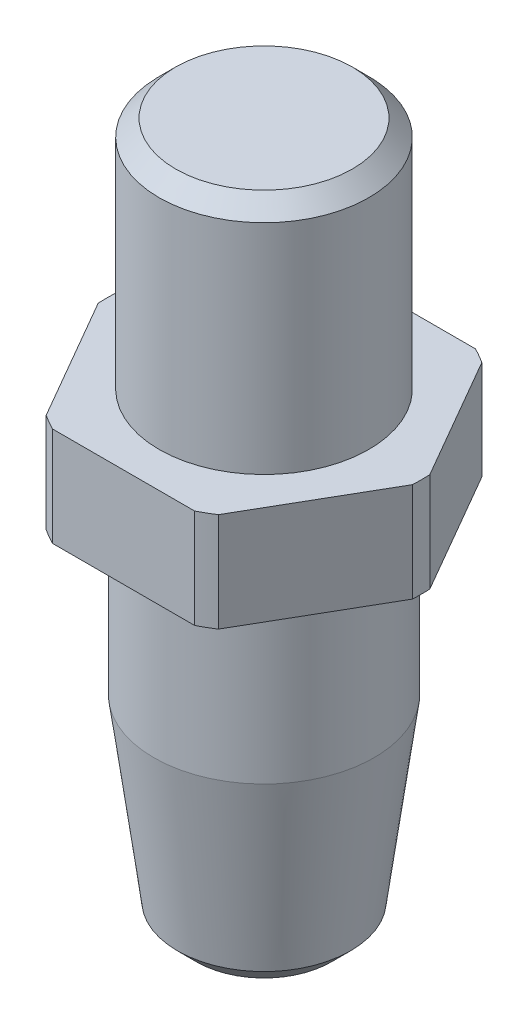
SolidWorks part; units mm, degrees
material "AISI 4340 Steel, normalized"
ref_plane "Front Plane" through (0, 0, 0) normal (0, 0, 1) x (1, 0, 0)
ref_plane "Top Plane" through (0, 0, 0) normal (0, 1, 0) x (1, 0, 0)
ref_plane "Right Plane" through (0, 0, 0) normal (1, 0, 0) x (0, 0, -1)
sketch "Sketch1" plane through (0, 0, 0) normal (0, 0, 1) x (1, 0, 0)
  line L0 (-6.6675, 0) -> (-9.525, 0)
  line L1 (-9.525, 0) -> (-9.525, 6)
  line L2 (-9.525, 6) -> (-6.35, 6)
  line L3 (-6.35, 6) -> (-6.35, 20.2)
  line L4 (0, 72.0465) -> (0, -75.2102) construction
  line L5 (-6.35, 20.2) -> (0, 20.2)
  line L6 (-6.6675, 0) -> (-6.6675, -10)
  line L7 (-6.6675, -22) -> (-5.08, -22) construction
  line L8 (0, 20.2) -> (0, -22)
  line L9 (-6.6675, -10) -> (-5.08, -22)
  line L10 (-6.6675, -10) -> (-6.6675, -22) construction
  line L11 (-5.08, -22) -> (0, -22)
  dimension "D1" = 19.05
  dimension "D2" = 6
  dimension "D3" = 13.335
  dimension "D4" = 14.2
  dimension "D5" = 10
  dimension "D6" = 12.7
  dimension "D7" = 10.16
  dimension "D8" = 12
  dimension "D9" = 42.2
revolve "Revolve1" add sketch "Sketch1" angle 360 about L4
cosmetic thread "Cosmetic Thread1" parameters "D1"=9, "D2"=11.1887
chamfer "Chamfer1" distance 1 angle 45 2 edges at (0, 20.2, 6.35) (0, -22, 5.08) first distance on face at (0, 6, 6.35) first distance on face at (0, -22, 5.08)
sketch "Sketch2" plane through (0, 0, 0) normal (0, 0, 1) x (1, 0, 0)
  line L0 (0, -14.5914) -> (0, 22.8649) construction
fillet "Fillet1" [suppressed] radius 0.5
sketch "Sketch3" plane through (0, 0, 0) normal (1, 0, 0) x (0, 0, -1)
  line L0 (-6.6675, -10) -> (6.6675, -10) construction
  line L1 (-5.5118, -10) -> (-10.8903, -10)
  line L2 (-5.5118, -10) -> (-5.5118, -21.5593)
  line L3 (-5.5118, -21.5593) -> (-10.8903, -21.5593)
  line L4 (-10.8903, -10) -> (-10.8903, -21.5593)
  line L5 (0, 0) -> (0, -23.7447) construction
  line L6 (10.8903, -10) -> (10.8903, -21.5593)
  line L7 (5.5118, -21.5593) -> (10.8903, -21.5593)
  line L8 (5.5118, -10) -> (5.5118, -21.5593)
  line L9 (5.5118, -10) -> (10.8903, -10)
  dimension "D1" = 11.0236
extrude "Cut-Extrude1" [suppressed] cut sketch "Sketch3" against normal through all and the other way through all
sketch "Sketch4" plane through (0, 0, 0) normal (0, 1, 0) x (1, 0, 0)
  line L1 (9.815, 0) -> (4.9075, 8.5)
  line L2 (4.9075, 8.5) -> (-4.9075, 8.5)
  line L3 (-4.9075, 8.5) -> (-9.815, 0)
  line L4 (-9.815, 0) -> (-4.9075, -8.5)
  line L5 (-4.9075, -8.5) -> (4.9075, -8.5)
  line L6 (4.9075, -8.5) -> (9.815, 0)
  circle A0 centre (0, 0) radius 8.5 construction
  dimension "D1" = 17
extrude "Cut-Extrude3" cut sketch "Sketch4" along normal through all flip side to cut
move or copy body "Body-Move/Copy1" [suppressed] bodies to move or copy 101
